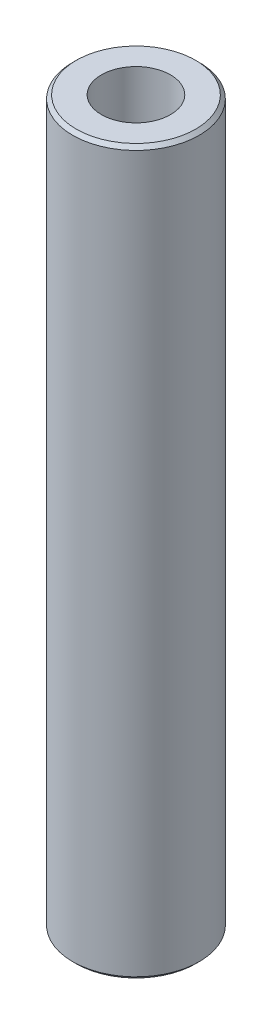
SolidWorks part; units mm, degrees
ref_plane "Front Plane" through (0, 0, 0) normal (0, 0, 1) x (1, 0, 0)
ref_plane "Top Plane" through (0, 0, 0) normal (0, 1, 0) x (1, 0, 0)
ref_plane "Right Plane" through (0, 0, 0) normal (1, 0, 0) x (0, 0, -1)
sketch "Sketch1" plane through (0, 0, 0) normal (0, 1, 0) x (1, 0, 0)
  circle A0 centre (0, 0) radius 52.5
  dimension "SHAFT_OD" = 105
extrude "Boss-Extrude1" add sketch "Sketch1" along normal blind 600
sketch "Sketch2" plane through (0, 0, 0) normal (0, 1, 0) x (1, 0, 0)
  circle A0 centre (0, 0) radius 28.6669
  dimension "BORE_D" = 57.3339
extrude "Cut-Extrude1" cut sketch "Sketch2" along normal through all
chamfer "Chamfer1" distance 2.9526 angle 45 2 edges at (0, 600, 52.5) (0, 0, 52.5)
